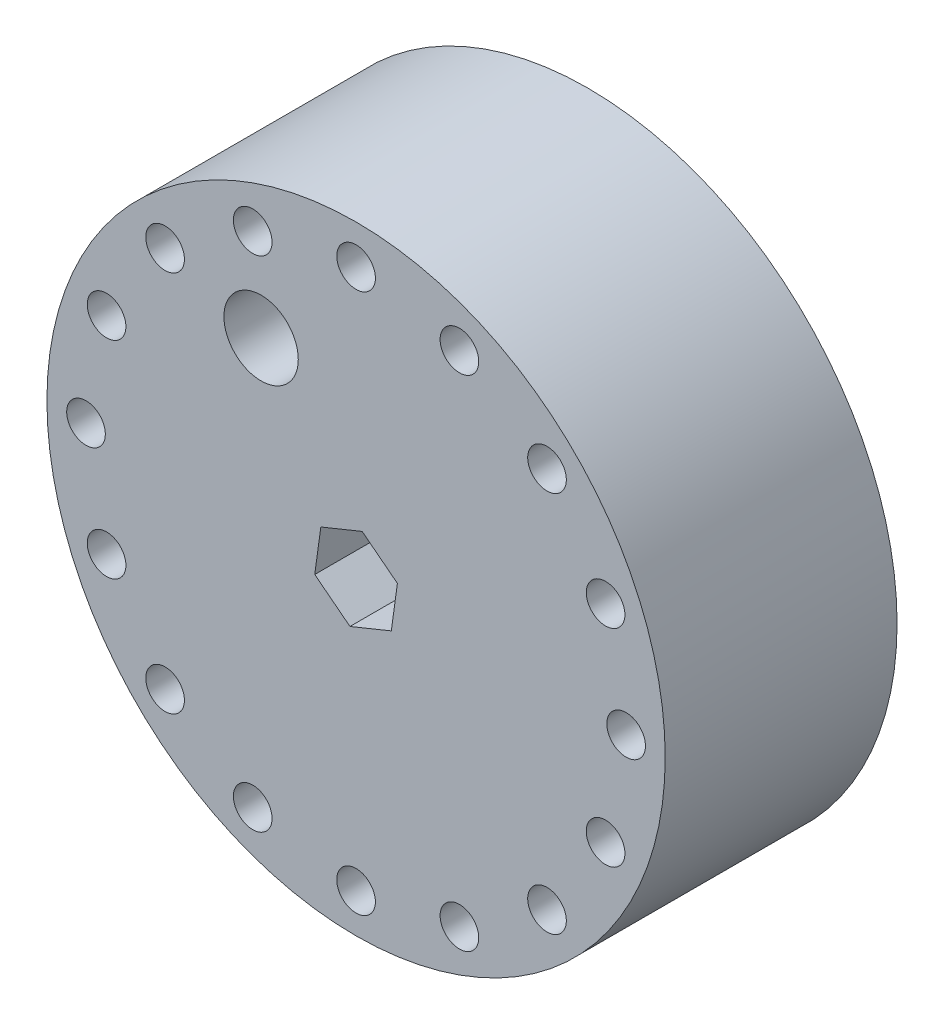
SolidWorks part; units mm, degrees
ref_plane "Front Plane" through (0, 0, 0) normal (0, 0, 1) x (1, 0, 0)
ref_plane "Top Plane" through (0, 0, 0) normal (0, 1, 0) x (1, 0, 0)
ref_plane "Right Plane" through (0, 0, 0) normal (1, 0, 0) x (0, 0, -1)
sketch "Sketch1" plane through (0, 0, 0) normal (0, 0, 1) x (1, 0, 0)
  line L1 (5.7893, -4.4996) -> (6.7915, 2.7639)
  line L2 (6.7915, 2.7639) -> (1.0021, 7.2635)
  line L3 (1.0021, 7.2635) -> (-5.7893, 4.4996)
  line L4 (-5.7893, 4.4996) -> (-6.7915, -2.7639)
  line L5 (-6.7915, -2.7639) -> (-1.0021, -7.2635)
  line L6 (-1.0021, -7.2635) -> (5.7893, -4.4996)
  circle A0 centre (0, 0) radius 50.8
  circle A1 centre (0, 0) radius 6.35 construction
  dimension "D2" = 101.6
  dimension "D1" = 12.7
extrude "Boss-Extrude1" add sketch "Sketch1" along normal blind 38.1
sketch "Sketch2" plane through (0, 0, 38.1) normal (0, 0, 1) x (1, 0, 0)
  circle A0 centre (0, 0) radius 44.3771 construction
  circle A1 centre (0, 44.3771) radius 3.175
  circle A2 centre (16.9824, 40.9991) radius 3.175
  circle A3 centre (31.3794, 31.3794) radius 3.175
  circle A4 centre (40.9991, 16.9824) radius 3.175
  circle A5 centre (44.3771, 0) radius 3.175
  circle A6 centre (40.9991, -16.9824) radius 3.175
  circle A7 centre (31.3794, -31.3794) radius 3.175
  circle A8 centre (16.9824, -40.9991) radius 3.175
  circle A9 centre (0, -44.3771) radius 3.175
  circle A10 centre (-16.9824, -40.9991) radius 3.175
  circle A11 centre (-31.3794, -31.3794) radius 3.175
  circle A12 centre (-40.9991, -16.9824) radius 3.175
  circle A13 centre (-44.3771, 0) radius 3.175
  circle A14 centre (-40.9991, 16.9824) radius 3.175
  circle A15 centre (-31.3794, 31.3794) radius 3.175
  circle A16 centre (-16.9824, 40.9991) radius 3.175
  point P37 (0, 0)
  dimension "D1" = 6.35
  dimension "D2" = 16
extrude "Cut-Extrude1" cut sketch "Sketch2" against normal through all
sketch "Sketch3" plane through (0, 0, 38.1) normal (0, 0, 1) x (1, 0, 0)
  circle A0 centre (-15.606, 26.4805) radius 6.1091
extrude "Cut-Extrude2" cut sketch "Sketch3" against normal through all
